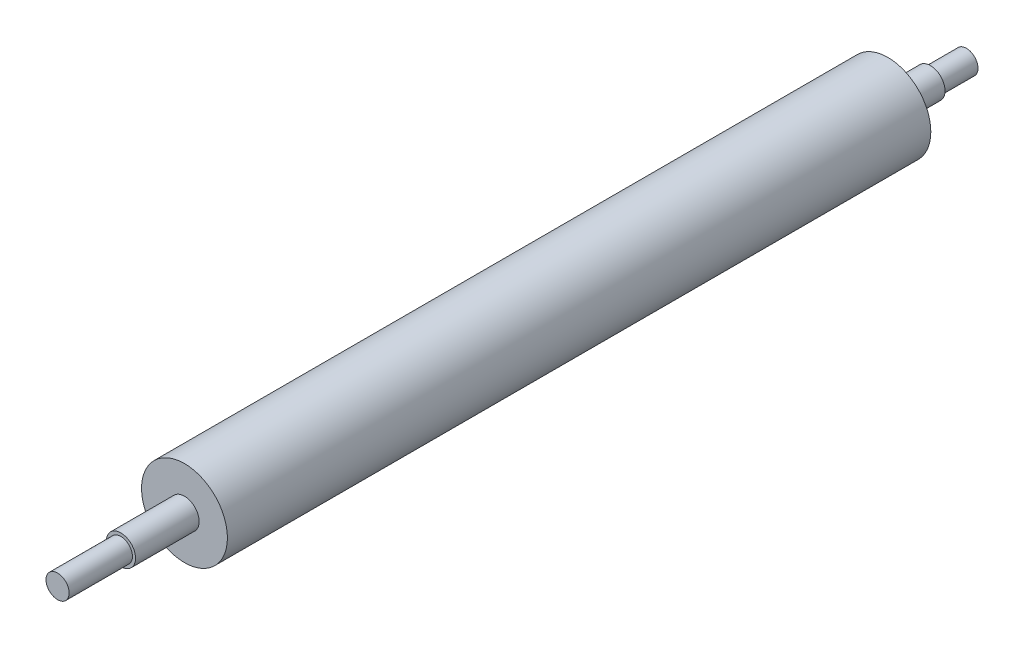
SolidWorks part; units mm, degrees
material "1060 Alloy"
ref_plane "Front Plane" through (0, 0, 0) normal (0, 0, 1) x (1, 0, 0)
ref_plane "Top Plane" through (0, 0, 0) normal (0, 1, 0) x (1, 0, 0)
ref_plane "Right Plane" through (0, 0, 0) normal (1, 0, 0) x (0, 0, -1)
sketch "Sketch1" plane through (0, 0, 0) normal (0, 0, 1) x (1, 0, 0)
  circle A0 centre (0, 0) radius 5
  circle A1 centre (0, 0) radius 3.95
  circle A2 centre (0, 0) radius 14.65
  dimension "D1" = 10
  dimension "D2" = 7.9
  dimension "D3" = 29.3
extrude "Boss-Extrude1" add sketch "Sketch1" along normal blind 240 contours A2 A0 | A0 A1 | A1 region at (-4.8586, 0, 0) region at (0, 0, 0) region at (-14.2356, 0, 0)
extrude "Boss-Extrude2" add sketch "Sketch1<3>" against normal blind 14.5 contours A0
sketch "Sketch1<3>" plane through (0, 0, 0) normal (0, 0, 1) x (1, 0, 0) same geometry as "Sketch1"
extrude "Boss-Extrude3" add sketch "Sketch1<4>" against normal blind 12.3 from surface contours A1 region at (0, 0, 0) starting at face at (5, 0, -14.5)
sketch "Sketch1<4>" plane through (0, 0, 0) normal (0, 0, 1) x (1, 0, 0) same geometry as "Sketch1"
extrude "Boss-Extrude4" add sketch "Sketch1<5>" along normal blind 21.7 from surface contours A1 | A0 A1 region at (-4.8586, 0, 0) region at (0, 0, 0) starting at face at (14.65, 0, 240)
sketch "Sketch1<5>" plane through (0, 0, 0) normal (0, 0, 1) x (1, 0, 0) same geometry as "Sketch1"
extrude "Boss-Extrude5" add sketch "Sketch1<6>" along normal blind 21.6 from surface contours A1 region at (0, 0, 0) starting at face at (5, 0, 261.7)
sketch "Sketch1<6>" plane through (0, 0, 0) normal (0, 0, 1) x (1, 0, 0) same geometry as "Sketch1"
